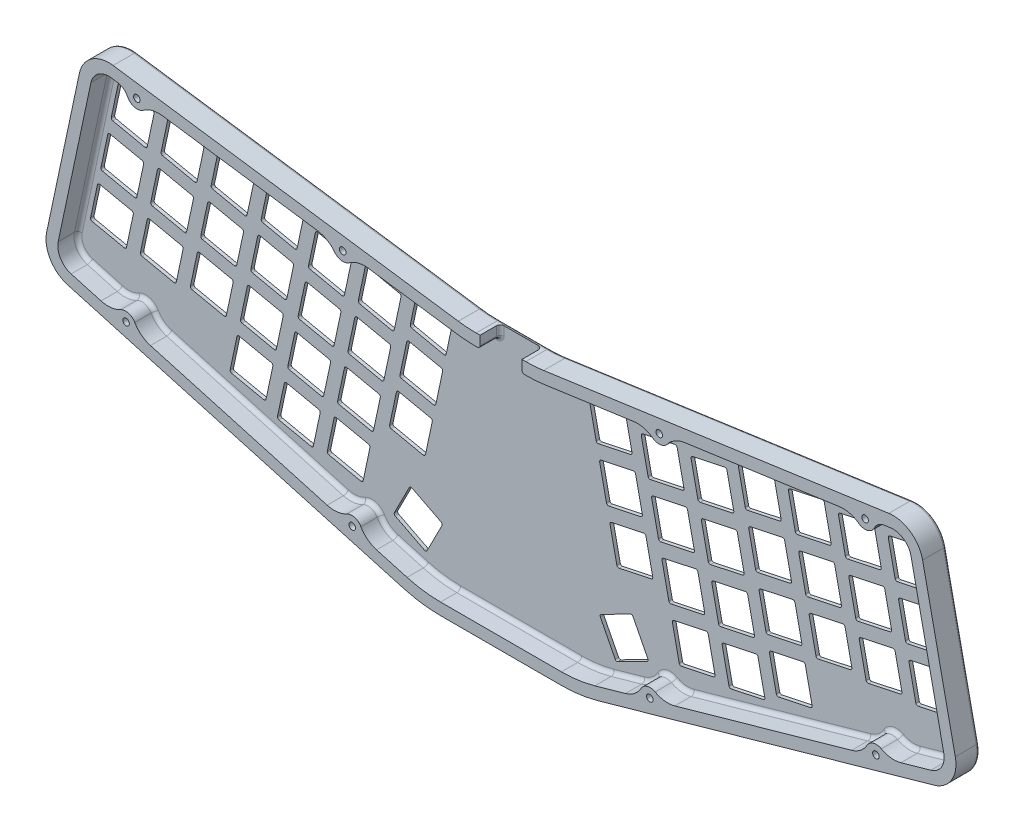
SolidWorks part; units mm, degrees
ref_plane "Front Plane" through (0, 0, 0) normal (0, 0, 1) x (1, 0, 0)
ref_plane "Top Plane" through (0, 0, 0) normal (0, 1, 0) x (1, 0, 0)
ref_plane "Right Plane" through (0, 0, 0) normal (1, 0, 0) x (0, 0, -1)
sketch "Model" plane through (0, 0, 0) normal (0, 0, 1) x (1, 0, 0)
  line L0 (7.1929, 63.9009) -> (19.4198, 61.302)
  line L1 (19.9974, 60.4125) -> (17.3986, 48.1856)
  line L2 (16.509, 47.6079) -> (4.2822, 50.2068)
  line L3 (3.7045, 51.0964) -> (6.3034, 63.3232)
  line L4 (3.2426, 45.3161) -> (15.4694, 42.7172)
  line L5 (16.0471, 41.8276) -> (13.4482, 29.6008)
  line L6 (12.5587, 29.0231) -> (0.3318, 31.622)
  line L7 (-0.2458, 32.5116) -> (2.3531, 44.7384)
  line L8 (-0.7077, 26.7313) -> (11.5191, 24.1324)
  line L9 (12.0968, 23.2428) -> (9.4979, 11.016)
  line L10 (8.6084, 10.4383) -> (-3.6185, 13.0372)
  line L11 (-4.1962, 13.9268) -> (-1.5973, 26.1536)
  line L12 (26.1936, 61.9069) -> (38.4204, 59.308)
  line L13 (38.9981, 58.4184) -> (36.3992, 46.1916)
  line L14 (35.5096, 45.6139) -> (23.2828, 48.2128)
  line L15 (22.7051, 49.1023) -> (25.304, 61.3292)
  line L16 (22.2432, 43.3221) -> (34.4701, 40.7232)
  line L17 (35.0478, 39.8336) -> (32.4489, 27.6068)
  line L18 (31.5593, 27.0291) -> (19.3325, 29.628)
  line L19 (18.7548, 30.5175) -> (21.3537, 42.7444)
  line L20 (18.2929, 24.7373) -> (30.5198, 22.1384)
  line L21 (31.0974, 21.2488) -> (28.4985, 9.022)
  line L22 (27.609, 8.4443) -> (15.3821, 11.0432)
  line L23 (14.8045, 11.9327) -> (17.4034, 24.1596)
  line L24 (45.2981, 60.4019) -> (57.525, 57.803)
  line L25 (58.1027, 56.9135) -> (55.5038, 44.6866)
  line L26 (54.6142, 44.109) -> (42.3874, 46.7078)
  line L27 (41.8097, 47.5974) -> (44.4086, 59.8242)
  line L28 (41.3478, 41.8171) -> (53.5747, 39.2182)
  line L29 (54.1523, 38.3287) -> (51.5534, 26.1018)
  line L30 (50.6639, 25.5241) -> (38.4371, 28.123)
  line L31 (37.8594, 29.0126) -> (40.4583, 41.2394)
  line L32 (37.3975, 23.2323) -> (49.6243, 20.6334)
  line L33 (50.202, 19.7439) -> (47.6031, 7.517)
  line L34 (46.7136, 6.9393) -> (34.4867, 9.5382)
  line L35 (33.9091, 10.4278) -> (36.5079, 22.6546)
  line L36 (64.4027, 58.897) -> (76.6296, 56.2981)
  line L37 (77.2072, 55.4085) -> (74.6083, 43.1817)
  line L38 (73.7188, 42.604) -> (61.492, 45.2029)
  line L39 (60.9143, 46.0924) -> (63.5132, 58.3193)
  line L40 (60.4524, 40.3122) -> (72.6792, 37.7133)
  line L41 (73.2569, 36.8237) -> (70.658, 24.5969)
  line L42 (69.7685, 24.0192) -> (57.5416, 26.6181)
  line L43 (56.964, 27.5076) -> (59.5629, 39.7345)
  line L44 (56.5021, 21.7274) -> (68.7289, 19.1285)
  line L45 (69.3066, 18.2389) -> (66.7077, 6.0121)
  line L46 (65.8182, 5.4344) -> (53.5913, 8.0333)
  line L47 (53.0136, 8.9228) -> (55.6125, 21.1497)
  line L48 (52.5518, 3.1425) -> (64.7786, 0.5437)
  line L49 (65.3563, -0.3459) -> (62.7574, -12.5727)
  line L50 (61.8678, -13.1504) -> (49.641, -10.5515)
  line L51 (49.0633, -9.662) -> (51.6622, 2.5649)
  line L52 (82.4677, 52.5013) -> (94.6946, 49.9024)
  line L53 (95.2723, 49.0128) -> (92.6734, 36.786)
  line L54 (91.7838, 36.2083) -> (79.557, 38.8072)
  line L55 (78.9793, 39.6967) -> (81.5782, 51.9236)
  line L56 (78.5174, 33.9165) -> (90.7443, 31.3176)
  line L57 (91.3219, 30.428) -> (88.723, 18.2012)
  line L58 (87.8335, 17.6235) -> (75.6067, 20.2224)
  line L59 (75.029, 21.1119) -> (77.6279, 33.3388)
  line L60 (74.5671, 15.3317) -> (86.7939, 12.7328)
  line L61 (87.3716, 11.8432) -> (84.7727, -0.3836)
  line L62 (83.8832, -0.9613) -> (71.6563, 1.6376)
  line L63 (71.0787, 2.5271) -> (73.6776, 14.754)
  line L64 (101.4684, 50.5072) -> (113.6952, 47.9083)
  line L65 (114.2729, 47.0188) -> (111.674, 34.792)
  line L66 (110.7845, 34.2143) -> (98.5576, 36.8132)
  line L67 (97.9799, 37.7027) -> (100.5788, 49.9296)
  line L68 (97.5181, 31.9224) -> (109.7449, 29.3235)
  line L69 (110.3226, 28.434) -> (107.7237, 16.2072)
  line L70 (106.8341, 15.6295) -> (94.6073, 18.2284)
  line L71 (94.0296, 19.1179) -> (96.6285, 31.3448)
  line L72 (93.5677, 13.3376) -> (105.7946, 10.7387)
  line L73 (106.3723, 9.8492) -> (103.7734, -2.3777)
  line L74 (102.8838, -2.9553) -> (90.657, -0.3564)
  line L75 (90.0793, 0.5331) -> (92.6782, 12.76)
  line L76 (134.1052, 48.9374) -> (131.5063, 36.7105)
  line L77 (130.6167, 36.1328) -> (118.3899, 38.7317)
  line L78 (117.8122, 39.6213) -> (120.4111, 51.8481)
  line L79 (117.3503, 33.841) -> (129.5772, 31.2421)
  line L80 (130.1548, 30.3526) -> (127.556, 18.1257)
  line L81 (126.6664, 17.548) -> (114.4396, 20.1469)
  line L82 (113.8619, 21.0365) -> (116.4608, 33.2633)
  line L83 (113.4, 15.2562) -> (125.6268, 12.6573)
  line L84 (126.2045, 11.7678) -> (123.6056, -0.4591)
  line L85 (122.7161, -1.0368) -> (110.4892, 1.5621)
  line L86 (109.9116, 2.4517) -> (112.5105, 14.6785)
  line L87 (70.6168, -3.2531) -> (82.8436, -5.852)
  line L88 (83.4213, -6.7416) -> (80.8224, -18.9684)
  line L89 (79.9329, -19.5461) -> (67.706, -16.9472)
  line L90 (67.1283, -16.0577) -> (69.7272, -3.8308)
  line L91 (89.6174, -5.2472) -> (101.8443, -7.8461)
  line L92 (102.4219, -8.7356) -> (99.823, -20.9625)
  line L93 (98.9335, -21.5401) -> (86.7066, -18.9412)
  line L94 (86.129, -18.0517) -> (88.7279, -5.8248)
  line L95 (117.654, -29.3648) -> (112.0852, -26.5274)
  line L96 (111.7574, -25.5186) -> (117.4323, -14.381)
  line L97 (118.4411, -14.0533) -> (129.5787, -19.7282)
  line L98 (129.9064, -20.7369) -> (124.2315, -31.8745)
  line L99 (123.2228, -32.2023) -> (117.654, -29.3648)
  line L100 (112.629, -33.5493) -> (124.2783, -36.8388)
  line L101 (137.0504, -38.6074) -> (160.1264, -38.6074)
  line L102 (160.1264, -38.6074) -> (183.2025, -38.6074)
  line L103 (195.9746, -36.8388) -> (207.6239, -33.5493)
  line L104 (226.4824, -28.2242) -> (271.949, -15.3856)
  line L105 (271.949, -15.3856) -> (293.9202, -9.1816)
  line L106 (210.7632, 57.9332) -> (177.0346, 53.1572)
  line L107 (169.604, 52.6338) -> (150.6488, 52.6338)
  line L108 (143.2182, 53.1572) -> (109.4896, 57.9332)
  line L109 (90.0873, 60.6806) -> (30.9176, 69.0589)
  line L110 (289.3352, 69.0589) -> (230.1656, 60.6806)
  line L111 (26.3327, -9.1816) -> (48.3039, -15.3856)
  line L112 (48.3039, -15.3856) -> (93.7705, -28.2242)
  line L113 (312.7787, -3.8564) -> (324.1811, -0.6367)
  line L114 (-2.1254, 39.3007) -> (3.622, 66.34)
  line L115 (-2.1254, 39.3007) -> (-8.8731, 7.5553)
  line L116 (13.8071, 71.4818) -> (11.4504, 71.8155)
  line L117 (-3.9283, -0.6367) -> (7.4742, -3.8564)
  line L118 (306.4458, 71.4818) -> (308.8024, 71.8155)
  line L119 (322.3782, 39.3007) -> (329.1259, 7.5553)
  line L120 (322.3782, 39.3007) -> (316.6308, 66.34)
  line L121 (121.3006, 52.4258) -> (133.5275, 49.8269)
  line L122 (313.0599, 63.9009) -> (300.8331, 61.302)
  line L123 (300.2554, 60.4125) -> (302.8543, 48.1856)
  line L124 (303.7438, 47.6079) -> (315.9707, 50.2068)
  line L125 (316.5483, 51.0964) -> (313.9494, 63.3232)
  line L126 (317.0102, 45.3161) -> (304.7834, 42.7172)
  line L127 (304.2057, 41.8276) -> (306.8046, 29.6008)
  line L128 (307.6941, 29.0231) -> (319.921, 31.622)
  line L129 (320.4987, 32.5116) -> (317.8998, 44.7384)
  line L130 (320.9605, 26.7313) -> (308.7337, 24.1324)
  line L131 (308.156, 23.2428) -> (310.7549, 11.016)
  line L132 (311.6445, 10.4383) -> (323.8713, 13.0372)
  line L133 (324.449, 13.9268) -> (321.8501, 26.1536)
  line L134 (294.0593, 61.9069) -> (281.8324, 59.308)
  line L135 (281.2548, 58.4184) -> (283.8536, 46.1916)
  line L136 (284.7432, 45.6139) -> (296.97, 48.2128)
  line L137 (297.5477, 49.1023) -> (294.9488, 61.3292)
  line L138 (298.0096, 43.3221) -> (285.7828, 40.7232)
  line L139 (285.2051, 39.8336) -> (287.804, 27.6068)
  line L140 (288.6935, 27.0291) -> (300.9204, 29.628)
  line L141 (301.498, 30.5175) -> (298.8991, 42.7444)
  line L142 (301.9599, 24.7373) -> (289.7331, 22.1384)
  line L143 (289.1554, 21.2488) -> (291.7543, 9.022)
  line L144 (292.6438, 8.4443) -> (304.8707, 11.0432)
  line L145 (305.4484, 11.9327) -> (302.8495, 24.1596)
  line L146 (274.9547, 60.4019) -> (262.7278, 57.803)
  line L147 (262.1502, 56.9135) -> (264.7491, 44.6866)
  line L148 (265.6386, 44.109) -> (277.8655, 46.7078)
  line L149 (278.4431, 47.5974) -> (275.8442, 59.8242)
  line L150 (278.905, 41.8171) -> (266.6782, 39.2182)
  line L151 (266.1005, 38.3287) -> (268.6994, 26.1018)
  line L152 (269.5889, 25.5241) -> (281.8158, 28.123)
  line L153 (282.3935, 29.0126) -> (279.7946, 41.2394)
  line L154 (282.8553, 23.2323) -> (270.6285, 20.6334)
  line L155 (270.0508, 19.7439) -> (272.6497, 7.517)
  line L156 (273.5393, 6.9393) -> (285.7661, 9.5382)
  line L157 (286.3438, 10.4278) -> (283.7449, 22.6546)
  line L158 (255.8501, 58.897) -> (243.6233, 56.2981)
  line L159 (243.0456, 55.4085) -> (245.6445, 43.1817)
  line L160 (246.534, 42.604) -> (258.7609, 45.2029)
  line L161 (259.3385, 46.0924) -> (256.7397, 58.3193)
  line L162 (259.8004, 40.3122) -> (247.5736, 37.7133)
  line L163 (246.9959, 36.8237) -> (249.5948, 24.5969)
  line L164 (250.4843, 24.0192) -> (262.7112, 26.6181)
  line L165 (263.2889, 27.5076) -> (260.69, 39.7345)
  line L166 (263.7508, 21.7274) -> (251.5239, 19.1285)
  line L167 (250.9462, 18.2389) -> (253.5451, 6.0121)
  line L168 (254.4347, 5.4344) -> (266.6615, 8.0333)
  line L169 (267.2392, 8.9228) -> (264.6403, 21.1497)
  line L170 (267.7011, 3.1425) -> (255.4742, 0.5437)
  line L171 (254.8966, -0.3459) -> (257.4954, -12.5727)
  line L172 (258.385, -13.1504) -> (270.6118, -10.5515)
  line L173 (271.1895, -9.662) -> (268.5906, 2.5649)
  line L174 (237.7851, 52.5013) -> (225.5582, 49.9024)
  line L175 (224.9806, 49.0128) -> (227.5795, 36.786)
  line L176 (228.469, 36.2083) -> (240.6958, 38.8072)
  line L177 (241.2735, 39.6967) -> (238.6746, 51.9236)
  line L178 (241.7354, 33.9165) -> (229.5086, 31.3176)
  line L179 (228.9309, 30.428) -> (231.5298, 18.2012)
  line L180 (232.4193, 17.6235) -> (244.6462, 20.2224)
  line L181 (245.2238, 21.1119) -> (242.6249, 33.3388)
  line L182 (245.6857, 15.3317) -> (233.4589, 12.7328)
  line L183 (232.8812, 11.8432) -> (235.4801, -0.3836)
  line L184 (236.3696, -0.9613) -> (248.5965, 1.6376)
  line L185 (249.1742, 2.5271) -> (246.5753, 14.754)
  line L186 (218.7845, 50.5072) -> (206.5576, 47.9083)
  line L187 (205.9799, 47.0188) -> (208.5788, 34.792)
  line L188 (209.4684, 34.2143) -> (221.6952, 36.8132)
  line L189 (222.2729, 37.7027) -> (219.674, 49.9296)
  line L190 (222.7348, 31.9224) -> (210.5079, 29.3235)
  line L191 (209.9303, 28.434) -> (212.5292, 16.2072)
  line L192 (213.4187, 15.6295) -> (225.6455, 18.2284)
  line L193 (226.2232, 19.1179) -> (223.6243, 31.3448)
  line L194 (226.6851, 13.3376) -> (214.4583, 10.7387)
  line L195 (213.8806, 9.8492) -> (216.4795, -2.3777)
  line L196 (217.369, -2.9553) -> (229.5959, -0.3564)
  line L197 (230.1735, 0.5331) -> (227.5746, 12.76)
  line L198 (186.1477, 48.9374) -> (188.7466, 36.7105)
  line L199 (189.6361, 36.1328) -> (201.8629, 38.7317)
  line L200 (202.4406, 39.6213) -> (199.8417, 51.8481)
  line L201 (202.9025, 33.841) -> (190.6757, 31.2421)
  line L202 (190.098, 30.3526) -> (192.6969, 18.1257)
  line L203 (193.5864, 17.548) -> (205.8133, 20.1469)
  line L204 (206.3909, 21.0365) -> (203.792, 33.2633)
  line L205 (206.8528, 15.2562) -> (194.626, 12.6573)
  line L206 (194.0483, 11.7678) -> (196.6472, -0.4591)
  line L207 (197.5367, -1.0368) -> (209.7636, 1.5621)
  line L208 (210.3413, 2.4517) -> (207.7424, 14.6785)
  line L209 (249.636, -3.2531) -> (237.4092, -5.852)
  line L210 (236.8315, -6.7416) -> (239.4304, -18.9684)
  line L211 (240.32, -19.5461) -> (252.5468, -16.9472)
  line L212 (253.1245, -16.0577) -> (250.5256, -3.8308)
  line L213 (230.6354, -5.2472) -> (218.4086, -7.8461)
  line L214 (217.8309, -8.7356) -> (220.4298, -20.9625)
  line L215 (221.3193, -21.5401) -> (233.5462, -18.9412)
  line L216 (234.1239, -18.0517) -> (231.525, -5.8248)
  line L217 (202.5988, -29.3648) -> (208.1676, -26.5274)
  line L218 (208.4954, -25.5186) -> (202.8205, -14.381)
  line L219 (201.8118, -14.0533) -> (190.6742, -19.7282)
  line L220 (190.3464, -20.7369) -> (196.0213, -31.8745)
  line L221 (197.03, -32.2023) -> (202.5988, -29.3648)
  line L222 (198.9522, 52.4258) -> (186.7253, 49.8269)
  line L223 (169.604, 55.6338) -> (150.6488, 55.6338)
  line L224 (143.6388, 56.1276) -> (11.8711, 74.7858)
  line L225 (0.6876, 66.9637) -> (-5.0598, 39.9244)
  line L226 (-5.0598, 39.9244) -> (-11.8075, 8.179)
  line L227 (-4.7435, -3.5238) -> (47.4886, -18.2727)
  line L228 (47.4886, -18.2727) -> (123.463, -39.7259)
  line L229 (137.0504, -41.6074) -> (160.1264, -41.6074)
  line L230 (160.1264, -41.6074) -> (183.2025, -41.6074)
  line L231 (196.7898, -39.7259) -> (272.7642, -18.2727)
  line L232 (272.7642, -18.2727) -> (324.9963, -3.5238)
  line L233 (332.0603, 8.179) -> (325.3126, 39.9244)
  line L234 (325.3126, 39.9244) -> (319.5653, 66.9637)
  line L235 (308.3818, 74.7858) -> (176.614, 56.1276)
  line L236 (169.604, 57.1338) -> (150.6488, 57.1338)
  line L237 (143.8491, 57.6128) -> (12.0814, 76.271)
  line L238 (-0.7797, 67.2756) -> (-6.527, 40.2363)
  line L239 (-6.527, 40.2363) -> (-13.2747, 8.4909)
  line L240 (-5.1511, -4.9673) -> (47.081, -19.7163)
  line L241 (47.081, -19.7163) -> (123.0554, -41.1694)
  line L242 (137.0504, -43.1074) -> (160.1264, -43.1074)
  line L243 (160.1264, -43.1074) -> (183.2025, -43.1074)
  line L244 (197.1974, -41.1694) -> (273.1718, -19.7163)
  line L245 (273.1718, -19.7163) -> (325.404, -4.9673)
  line L246 (333.5276, 8.4909) -> (326.7799, 40.2363)
  line L247 (326.7799, 40.2363) -> (321.0325, 67.2756)
  line L248 (308.1715, 76.271) -> (176.4037, 57.6128)
  arc A0 (106.6702, -28.8979) -> (101.2821, -27.3764) centre (103.1997, -30.8868) ccw
  arc A1 (93.7705, -28.2242) -> (101.2821, -27.3764) centre (96.4879, -18.6005) ccw
  arc A2 (106.6702, -28.8979) -> (112.629, -33.5493) centre (115.3464, -23.9256) ccw
  circle A3 centre (103.3356, -30.4056) radius 1.25
  arc A4 (207.6239, -33.5493) -> (213.5826, -28.8979) centre (204.9064, -23.9256) ccw
  arc A5 (218.9708, -27.3764) -> (226.4824, -28.2242) centre (223.7649, -18.6005) ccw
  arc A6 (218.9708, -27.3764) -> (213.5826, -28.8979) centre (217.0531, -30.8868) ccw
  circle A7 centre (216.9173, -30.4056) radius 1.25
  arc A8 (218.0932, 56.0855) -> (223.6367, 56.8704) centre (220.4644, 59.3069) ccw
  arc A9 (96.6161, 56.8704) -> (102.1596, 56.0855) centre (99.7884, 59.3069) ccw
  arc A10 (109.4896, 57.9332) -> (102.1596, 56.0855) centre (108.0876, 48.032) ccw
  arc A11 (96.6161, 56.8704) -> (90.0873, 60.6806) centre (88.6852, 50.7793) ccw
  arc A12 (218.0932, 56.0855) -> (210.7632, 57.9332) centre (212.1652, 48.032) ccw
  arc A13 (230.1656, 60.6806) -> (223.6367, 56.8704) centre (231.5676, 50.7793) ccw
  circle A14 centre (99.7183, 58.8118) radius 1.25
  circle A15 centre (220.5345, 58.8118) radius 1.25
  arc A16 (305.2671, -3.0086) -> (299.8789, -4.5301) centre (303.3494, -6.519) ccw
  arc A17 (20.3739, -4.5301) -> (14.9858, -3.0086) centre (16.9034, -6.519) ccw
  arc A18 (20.3739, -4.5301) -> (26.3327, -9.1816) centre (29.0501, 0.4421) ccw
  arc A19 (305.2671, -3.0086) -> (312.7787, -3.8564) centre (310.0612, 5.7673) ccw
  arc A20 (293.9202, -9.1816) -> (299.8789, -4.5301) centre (291.2027, 0.4421) ccw
  arc A21 (7.4742, -3.8564) -> (14.9858, -3.0086) centre (10.1916, 5.7673) ccw
  circle A22 centre (17.0393, -6.0378) radius 1.25
  circle A23 centre (303.2135, -6.0378) radius 1.25
  arc A24 (-8.8731, 7.5553) -> (-3.9283, -0.6367) centre (-2.026, 6.0999) ccw
  arc A25 (11.4504, 71.8155) -> (3.622, 66.34) centre (10.469, 64.8846) ccw
  arc A26 (316.6308, 66.34) -> (308.8024, 71.8155) centre (309.7838, 64.8846) ccw
  arc A27 (324.1811, -0.6367) -> (329.1259, 7.5553) centre (322.2789, 6.0999) ccw
  arc A28 (296.6652, 67.2112) -> (302.641, 68.6986) centre (299.0364, 70.4326) ccw
  arc A29 (17.6118, 68.6986) -> (23.5876, 67.2112) centre (21.2165, 70.4326) ccw
  arc A30 (30.9176, 69.0589) -> (23.5876, 67.2112) centre (29.5156, 59.1577) ccw
  arc A31 (17.6118, 68.6986) -> (13.8071, 71.4818) centre (13.106, 66.5312) ccw
  arc A32 (306.4458, 71.4818) -> (302.641, 68.6986) centre (307.1468, 66.5312) ccw
  arc A33 (296.6652, 67.2112) -> (289.3352, 69.0589) centre (290.7372, 59.1577) ccw
  circle A34 centre (299.1065, 69.9376) radius 1.25
  circle A35 centre (21.1464, 69.9376) radius 1.25
  arc A36 (3.7045, 51.0964) -> (4.2822, 50.2068) centre (4.4381, 50.9404) ccw
  arc A37 (7.1929, 63.9009) -> (6.3034, 63.3232) centre (7.037, 63.1673) ccw
  arc A38 (19.9974, 60.4125) -> (19.4198, 61.302) centre (19.2638, 60.5684) ccw
  arc A39 (16.509, 47.6079) -> (17.3986, 48.1856) centre (16.6649, 48.3415) ccw
  arc A40 (3.2426, 45.3161) -> (2.3531, 44.7384) centre (3.0867, 44.5825) ccw
  arc A41 (-0.2458, 32.5116) -> (0.3318, 31.622) centre (0.4878, 32.3556) ccw
  arc A42 (12.5587, 29.0231) -> (13.4482, 29.6008) centre (12.7146, 29.7567) ccw
  arc A43 (16.0471, 41.8276) -> (15.4694, 42.7172) centre (15.3135, 41.9836) ccw
  arc A44 (-0.7077, 26.7313) -> (-1.5973, 26.1536) centre (-0.8637, 25.9977) ccw
  arc A45 (-4.1962, 13.9268) -> (-3.6185, 13.0372) centre (-3.4625, 13.7708) ccw
  arc A46 (8.6084, 10.4383) -> (9.4979, 11.016) centre (8.7643, 11.1719) ccw
  arc A47 (12.0968, 23.2428) -> (11.5191, 24.1324) centre (11.3632, 23.3988) ccw
  arc A48 (14.8045, 11.9327) -> (15.3821, 11.0432) centre (15.5381, 11.7768) ccw
  arc A49 (27.609, 8.4443) -> (28.4985, 9.022) centre (27.7649, 9.1779) ccw
  arc A50 (31.0974, 21.2488) -> (30.5198, 22.1384) centre (30.3638, 21.4048) ccw
  arc A51 (18.2929, 24.7373) -> (17.4034, 24.1596) centre (18.137, 24.0036) ccw
  arc A52 (18.7548, 30.5175) -> (19.3325, 29.628) centre (19.4884, 30.3616) ccw
  arc A53 (31.5593, 27.0291) -> (32.4489, 27.6068) centre (31.7152, 27.7627) ccw
  arc A54 (35.0478, 39.8336) -> (34.4701, 40.7232) centre (34.3141, 39.9896) ccw
  arc A55 (22.2432, 43.3221) -> (21.3537, 42.7444) centre (22.0873, 42.5885) ccw
  arc A56 (22.7051, 49.1023) -> (23.2828, 48.2128) centre (23.4387, 48.9464) ccw
  arc A57 (35.5096, 45.6139) -> (36.3992, 46.1916) centre (35.6656, 46.3475) ccw
  arc A58 (38.9981, 58.4184) -> (38.4204, 59.308) centre (38.2645, 58.5744) ccw
  arc A59 (26.1936, 61.9069) -> (25.304, 61.3292) centre (26.0376, 61.1733) ccw
  arc A60 (33.9091, 10.4278) -> (34.4867, 9.5382) centre (34.6427, 10.2718) ccw
  arc A61 (37.3975, 23.2323) -> (36.5079, 22.6546) centre (37.2416, 22.4987) ccw
  arc A62 (50.202, 19.7439) -> (49.6243, 20.6334) centre (49.4684, 19.8998) ccw
  arc A63 (46.7136, 6.9393) -> (47.6031, 7.517) centre (46.8695, 7.673) ccw
  arc A64 (50.6639, 25.5241) -> (51.5534, 26.1018) centre (50.8198, 26.2578) ccw
  arc A65 (37.8594, 29.0126) -> (38.4371, 28.123) centre (38.593, 28.8567) ccw
  arc A66 (41.3478, 41.8171) -> (40.4583, 41.2394) centre (41.1919, 41.0835) ccw
  arc A67 (54.1523, 38.3287) -> (53.5747, 39.2182) centre (53.4187, 38.4846) ccw
  arc A68 (54.6142, 44.109) -> (55.5038, 44.6866) centre (54.7702, 44.8426) ccw
  arc A69 (41.8097, 47.5974) -> (42.3874, 46.7078) centre (42.5433, 47.4415) ccw
  arc A70 (45.2981, 60.4019) -> (44.4086, 59.8242) centre (45.1422, 59.6683) ccw
  arc A71 (58.1027, 56.9135) -> (57.525, 57.803) centre (57.369, 57.0694) ccw
  arc A72 (56.964, 27.5076) -> (57.5416, 26.6181) centre (57.6976, 27.3517) ccw
  arc A73 (60.4524, 40.3122) -> (59.5629, 39.7345) centre (60.2965, 39.5785) ccw
  arc A74 (73.2569, 36.8237) -> (72.6792, 37.7133) centre (72.5233, 36.9797) ccw
  arc A75 (69.7685, 24.0192) -> (70.658, 24.5969) centre (69.9244, 24.7528) ccw
  arc A76 (60.9143, 46.0924) -> (61.492, 45.2029) centre (61.6479, 45.9365) ccw
  arc A77 (73.7188, 42.604) -> (74.6083, 43.1817) centre (73.8747, 43.3376) ccw
  arc A78 (77.2072, 55.4085) -> (76.6296, 56.2981) centre (76.4736, 55.5645) ccw
  arc A79 (64.4027, 58.897) -> (63.5132, 58.3193) centre (64.2468, 58.1634) ccw
  arc A80 (53.0136, 8.9228) -> (53.5913, 8.0333) centre (53.7472, 8.7669) ccw
  arc A81 (56.5021, 21.7274) -> (55.6125, 21.1497) centre (56.3461, 20.9937) ccw
  arc A82 (69.3066, 18.2389) -> (68.7289, 19.1285) centre (68.573, 18.3948) ccw
  arc A83 (65.8182, 5.4344) -> (66.7077, 6.0121) centre (65.9741, 6.168) ccw
  arc A84 (49.0633, -9.662) -> (49.641, -10.5515) centre (49.7969, -9.8179) ccw
  arc A85 (52.5518, 3.1425) -> (51.6622, 2.5649) centre (52.3958, 2.4089) ccw
  arc A86 (65.3563, -0.3459) -> (64.7786, 0.5437) centre (64.6227, -0.19) ccw
  arc A87 (61.8678, -13.1504) -> (62.7574, -12.5727) centre (62.0238, -12.4168) ccw
  arc A88 (67.1283, -16.0577) -> (67.706, -16.9472) centre (67.8619, -16.2136) ccw
  arc A89 (70.6168, -3.2531) -> (69.7272, -3.8308) centre (70.4608, -3.9868) ccw
  arc A90 (83.4213, -6.7416) -> (82.8436, -5.852) centre (82.6877, -6.5856) ccw
  arc A91 (79.9329, -19.5461) -> (80.8224, -18.9684) centre (80.0888, -18.8125) ccw
  arc A92 (71.0787, 2.5271) -> (71.6563, 1.6376) centre (71.8123, 2.3712) ccw
  arc A93 (83.8832, -0.9613) -> (84.7727, -0.3836) centre (84.0391, -0.2277) ccw
  arc A94 (87.3716, 11.8432) -> (86.7939, 12.7328) centre (86.638, 11.9992) ccw
  arc A95 (74.5671, 15.3317) -> (73.6776, 14.754) centre (74.4112, 14.5981) ccw
  arc A96 (75.029, 21.1119) -> (75.6067, 20.2224) centre (75.7626, 20.956) ccw
  arc A97 (87.8335, 17.6235) -> (88.723, 18.2012) centre (87.9894, 18.3571) ccw
  arc A98 (91.3219, 30.428) -> (90.7443, 31.3176) centre (90.5883, 30.584) ccw
  arc A99 (78.5174, 33.9165) -> (77.6279, 33.3388) centre (78.3615, 33.1829) ccw
  arc A100 (78.9793, 39.6967) -> (79.557, 38.8072) centre (79.7129, 39.5408) ccw
  arc A101 (82.4677, 52.5013) -> (81.5782, 51.9236) centre (82.3118, 51.7677) ccw
  arc A102 (95.2723, 49.0128) -> (94.6946, 49.9024) centre (94.5387, 49.1688) ccw
  arc A103 (91.7838, 36.2083) -> (92.6734, 36.786) centre (91.9398, 36.9419) ccw
  arc A104 (97.9799, 37.7027) -> (98.5576, 36.8132) centre (98.7135, 37.5468) ccw
  arc A105 (101.4684, 50.5072) -> (100.5788, 49.9296) centre (101.3124, 49.7736) ccw
  arc A106 (114.2729, 47.0188) -> (113.6952, 47.9083) centre (113.5393, 47.1747) ccw
  arc A107 (110.7845, 34.2143) -> (111.674, 34.792) centre (110.9404, 34.9479) ccw
  arc A108 (97.5181, 31.9224) -> (96.6285, 31.3448) centre (97.3621, 31.1888) ccw
  arc A109 (110.3226, 28.434) -> (109.7449, 29.3235) centre (109.589, 28.5899) ccw
  arc A110 (106.8341, 15.6295) -> (107.7237, 16.2072) centre (106.9901, 16.3631) ccw
  arc A111 (94.0296, 19.1179) -> (94.6073, 18.2284) centre (94.7632, 18.962) ccw
  arc A112 (93.5677, 13.3376) -> (92.6782, 12.76) centre (93.4118, 12.604) ccw
  arc A113 (106.3723, 9.8492) -> (105.7946, 10.7387) centre (105.6386, 10.0051) ccw
  arc A114 (102.8838, -2.9553) -> (103.7734, -2.3777) centre (103.0397, -2.2217) ccw
  arc A115 (90.0793, 0.5331) -> (90.657, -0.3564) centre (90.8129, 0.3772) ccw
  arc A116 (89.6174, -5.2472) -> (88.7279, -5.8248) centre (89.4615, -5.9808) ccw
  arc A117 (102.4219, -8.7356) -> (101.8443, -7.8461) centre (101.6883, -8.5797) ccw
  arc A118 (98.9335, -21.5401) -> (99.823, -20.9625) centre (99.0894, -20.8065) ccw
  arc A119 (86.129, -18.0517) -> (86.7066, -18.9412) centre (86.8626, -18.2076) ccw
  arc A120 (111.7574, -25.5186) -> (112.0852, -26.5274) centre (112.4257, -25.8591) ccw
  arc A121 (118.4411, -14.0533) -> (117.4323, -14.381) centre (118.1006, -14.7215) ccw
  arc A122 (129.9064, -20.7369) -> (129.5787, -19.7282) centre (129.2382, -20.3964) ccw
  arc A123 (123.2228, -32.2023) -> (124.2315, -31.8745) centre (123.5633, -31.534) ccw
  arc A124 (109.9116, 2.4517) -> (110.4892, 1.5621) centre (110.6452, 2.2957) ccw
  arc A125 (122.7161, -1.0368) -> (123.6056, -0.4591) centre (122.872, -0.3032) ccw
  arc A126 (126.2045, 11.7678) -> (125.6268, 12.6573) centre (125.4709, 11.9237) ccw
  arc A127 (113.4, 15.2562) -> (112.5105, 14.6785) centre (113.2441, 14.5226) ccw
  arc A128 (113.8619, 21.0365) -> (114.4396, 20.1469) centre (114.5955, 20.8805) ccw
  arc A129 (126.6664, 17.548) -> (127.556, 18.1257) centre (126.8223, 18.2817) ccw
  arc A130 (130.1548, 30.3526) -> (129.5772, 31.2421) centre (129.4212, 30.5085) ccw
  arc A131 (117.3503, 33.841) -> (116.4608, 33.2633) centre (117.1944, 33.1074) ccw
  arc A132 (117.8122, 39.6213) -> (118.3899, 38.7317) centre (118.5458, 39.4654) ccw
  arc A133 (130.6167, 36.1328) -> (131.5063, 36.7105) centre (130.7727, 36.8665) ccw
  arc A134 (134.1052, 48.9374) -> (133.5275, 49.8269) centre (133.3716, 49.0933) ccw
  arc A135 (121.3006, 52.4258) -> (120.4111, 51.8481) centre (121.1447, 51.6922) ccw
  arc A136 (313.9494, 63.3232) -> (313.0599, 63.9009) centre (313.2158, 63.1673) ccw
  arc A137 (300.8331, 61.302) -> (300.2554, 60.4125) centre (300.989, 60.5684) ccw
  arc A138 (302.8543, 48.1856) -> (303.7438, 47.6079) centre (303.5879, 48.3415) ccw
  arc A139 (315.9707, 50.2068) -> (316.5483, 51.0964) centre (315.8147, 50.9404) ccw
  arc A140 (317.8998, 44.7384) -> (317.0102, 45.3161) centre (317.1662, 44.5825) ccw
  arc A141 (304.7834, 42.7172) -> (304.2057, 41.8276) centre (304.9393, 41.9836) ccw
  arc A142 (306.8046, 29.6008) -> (307.6941, 29.0231) centre (307.5382, 29.7567) ccw
  arc A143 (319.921, 31.622) -> (320.4987, 32.5116) centre (319.7651, 32.3556) ccw
  arc A144 (321.8501, 26.1536) -> (320.9605, 26.7313) centre (321.1165, 25.9977) ccw
  arc A145 (308.7337, 24.1324) -> (308.156, 23.2428) centre (308.8896, 23.3988) ccw
  arc A146 (310.7549, 11.016) -> (311.6445, 10.4383) centre (311.4885, 11.1719) ccw
  arc A147 (323.8713, 13.0372) -> (324.449, 13.9268) centre (323.7154, 13.7708) ccw
  arc A148 (294.9488, 61.3292) -> (294.0593, 61.9069) centre (294.2152, 61.1733) ccw
  arc A149 (281.8324, 59.308) -> (281.2548, 58.4184) centre (281.9884, 58.5744) ccw
  arc A150 (283.8536, 46.1916) -> (284.7432, 45.6139) centre (284.5873, 46.3475) ccw
  arc A151 (296.97, 48.2128) -> (297.5477, 49.1023) centre (296.8141, 48.9464) ccw
  arc A152 (298.8991, 42.7444) -> (298.0096, 43.3221) centre (298.1655, 42.5885) ccw
  arc A153 (285.7828, 40.7232) -> (285.2051, 39.8336) centre (285.9387, 39.9896) ccw
  arc A154 (287.804, 27.6068) -> (288.6935, 27.0291) centre (288.5376, 27.7627) ccw
  arc A155 (300.9204, 29.628) -> (301.498, 30.5175) centre (300.7644, 30.3616) ccw
  arc A156 (302.8495, 24.1596) -> (301.9599, 24.7373) centre (302.1159, 24.0036) ccw
  arc A157 (289.7331, 22.1384) -> (289.1554, 21.2488) centre (289.889, 21.4048) ccw
  arc A158 (291.7543, 9.022) -> (292.6438, 8.4443) centre (292.4879, 9.1779) ccw
  arc A159 (304.8707, 11.0432) -> (305.4484, 11.9327) centre (304.7147, 11.7768) ccw
  arc A160 (262.7278, 57.803) -> (262.1502, 56.9135) centre (262.8838, 57.0694) ccw
  arc A161 (275.8442, 59.8242) -> (274.9547, 60.4019) centre (275.1106, 59.6683) ccw
  arc A162 (264.7491, 44.6866) -> (265.6386, 44.109) centre (265.4827, 44.8426) ccw
  arc A163 (277.8655, 46.7078) -> (278.4431, 47.5974) centre (277.7095, 47.4415) ccw
  arc A164 (266.6782, 39.2182) -> (266.1005, 38.3287) centre (266.8341, 38.4846) ccw
  arc A165 (279.7946, 41.2394) -> (278.905, 41.8171) centre (279.0609, 41.0835) ccw
  arc A166 (268.6994, 26.1018) -> (269.5889, 25.5241) centre (269.433, 26.2578) ccw
  arc A167 (281.8158, 28.123) -> (282.3935, 29.0126) centre (281.6598, 28.8567) ccw
  arc A168 (270.6285, 20.6334) -> (270.0508, 19.7439) centre (270.7844, 19.8998) ccw
  arc A169 (283.7449, 22.6546) -> (282.8553, 23.2323) centre (283.0113, 22.4987) ccw
  arc A170 (272.6497, 7.517) -> (273.5393, 6.9393) centre (273.3833, 7.673) ccw
  arc A171 (285.7661, 9.5382) -> (286.3438, 10.4278) centre (285.6102, 10.2718) ccw
  arc A172 (256.7397, 58.3193) -> (255.8501, 58.897) centre (256.006, 58.1634) ccw
  arc A173 (243.6233, 56.2981) -> (243.0456, 55.4085) centre (243.7792, 55.5645) ccw
  arc A174 (245.6445, 43.1817) -> (246.534, 42.604) centre (246.3781, 43.3376) ccw
  arc A175 (258.7609, 45.2029) -> (259.3385, 46.0924) centre (258.6049, 45.9365) ccw
  arc A176 (247.5736, 37.7133) -> (246.9959, 36.8237) centre (247.7295, 36.9797) ccw
  arc A177 (260.69, 39.7345) -> (259.8004, 40.3122) centre (259.9564, 39.5785) ccw
  arc A178 (249.5948, 24.5969) -> (250.4843, 24.0192) centre (250.3284, 24.7528) ccw
  arc A179 (262.7112, 26.6181) -> (263.2889, 27.5076) centre (262.5553, 27.3517) ccw
  arc A180 (251.5239, 19.1285) -> (250.9462, 18.2389) centre (251.6798, 18.3948) ccw
  arc A181 (253.5451, 6.0121) -> (254.4347, 5.4344) centre (254.2787, 6.168) ccw
  arc A182 (264.6403, 21.1497) -> (263.7508, 21.7274) centre (263.9067, 20.9937) ccw
  arc A183 (266.6615, 8.0333) -> (267.2392, 8.9228) centre (266.5056, 8.7669) ccw
  arc A184 (255.4742, 0.5437) -> (254.8966, -0.3459) centre (255.6302, -0.19) ccw
  arc A185 (257.4954, -12.5727) -> (258.385, -13.1504) centre (258.2291, -12.4168) ccw
  arc A186 (268.5906, 2.5649) -> (267.7011, 3.1425) centre (267.857, 2.4089) ccw
  arc A187 (270.6118, -10.5515) -> (271.1895, -9.662) centre (270.4559, -9.8179) ccw
  arc A188 (225.5582, 49.9024) -> (224.9806, 49.0128) centre (225.7142, 49.1688) ccw
  arc A189 (238.6746, 51.9236) -> (237.7851, 52.5013) centre (237.941, 51.7677) ccw
  arc A190 (227.5795, 36.786) -> (228.469, 36.2083) centre (228.3131, 36.9419) ccw
  arc A191 (240.6958, 38.8072) -> (241.2735, 39.6967) centre (240.5399, 39.5408) ccw
  arc A192 (242.6249, 33.3388) -> (241.7354, 33.9165) centre (241.8913, 33.1829) ccw
  arc A193 (229.5086, 31.3176) -> (228.9309, 30.428) centre (229.6645, 30.584) ccw
  arc A194 (231.5298, 18.2012) -> (232.4193, 17.6235) centre (232.2634, 18.3571) ccw
  arc A195 (244.6462, 20.2224) -> (245.2238, 21.1119) centre (244.4902, 20.956) ccw
  arc A196 (246.5753, 14.754) -> (245.6857, 15.3317) centre (245.8417, 14.5981) ccw
  arc A197 (233.4589, 12.7328) -> (232.8812, 11.8432) centre (233.6148, 11.9992) ccw
  arc A198 (235.4801, -0.3836) -> (236.3696, -0.9613) centre (236.2137, -0.2277) ccw
  arc A199 (248.5965, 1.6376) -> (249.1742, 2.5271) centre (248.4406, 2.3712) ccw
  arc A200 (206.5576, 47.9083) -> (205.9799, 47.0188) centre (206.7135, 47.1747) ccw
  arc A201 (219.674, 49.9296) -> (218.7845, 50.5072) centre (218.9404, 49.7736) ccw
  arc A202 (208.5788, 34.792) -> (209.4684, 34.2143) centre (209.3124, 34.9479) ccw
  arc A203 (221.6952, 36.8132) -> (222.2729, 37.7027) centre (221.5393, 37.5468) ccw
  arc A204 (210.5079, 29.3235) -> (209.9303, 28.434) centre (210.6639, 28.5899) ccw
  arc A205 (223.6243, 31.3448) -> (222.7348, 31.9224) centre (222.8907, 31.1888) ccw
  arc A206 (212.5292, 16.2072) -> (213.4187, 15.6295) centre (213.2628, 16.3631) ccw
  arc A207 (225.6455, 18.2284) -> (226.2232, 19.1179) centre (225.4896, 18.962) ccw
  arc A208 (227.5746, 12.76) -> (226.6851, 13.3376) centre (226.841, 12.604) ccw
  arc A209 (216.4795, -2.3777) -> (217.369, -2.9553) centre (217.2131, -2.2217) ccw
  arc A210 (214.4583, 10.7387) -> (213.8806, 9.8492) centre (214.6142, 10.0051) ccw
  arc A211 (229.5959, -0.3564) -> (230.1735, 0.5331) centre (229.4399, 0.3772) ccw
  arc A212 (199.8417, 51.8481) -> (198.9522, 52.4258) centre (199.1081, 51.6922) ccw
  arc A213 (186.7253, 49.8269) -> (186.1477, 48.9374) centre (186.8813, 49.0933) ccw
  arc A214 (188.7466, 36.7105) -> (189.6361, 36.1328) centre (189.4802, 36.8665) ccw
  arc A215 (201.8629, 38.7317) -> (202.4406, 39.6213) centre (201.707, 39.4654) ccw
  arc A216 (203.792, 33.2633) -> (202.9025, 33.841) centre (203.0584, 33.1074) ccw
  arc A217 (190.6757, 31.2421) -> (190.098, 30.3526) centre (190.8316, 30.5085) ccw
  arc A218 (192.6969, 18.1257) -> (193.5864, 17.548) centre (193.4305, 18.2817) ccw
  arc A219 (205.8133, 20.1469) -> (206.3909, 21.0365) centre (205.6573, 20.8805) ccw
  arc A220 (207.7424, 14.6785) -> (206.8528, 15.2562) centre (207.0088, 14.5226) ccw
  arc A221 (194.626, 12.6573) -> (194.0483, 11.7678) centre (194.7819, 11.9237) ccw
  arc A222 (196.6472, -0.4591) -> (197.5367, -1.0368) centre (197.3808, -0.3032) ccw
  arc A223 (209.7636, 1.5621) -> (210.3413, 2.4517) centre (209.6077, 2.2957) ccw
  arc A224 (250.5256, -3.8308) -> (249.636, -3.2531) centre (249.792, -3.9868) ccw
  arc A225 (239.4304, -18.9684) -> (240.32, -19.5461) centre (240.164, -18.8125) ccw
  arc A226 (237.4092, -5.852) -> (236.8315, -6.7416) centre (237.5651, -6.5856) ccw
  arc A227 (252.5468, -16.9472) -> (253.1245, -16.0577) centre (252.3909, -16.2136) ccw
  arc A228 (218.4086, -7.8461) -> (217.8309, -8.7356) centre (218.5645, -8.5797) ccw
  arc A229 (231.525, -5.8248) -> (230.6354, -5.2472) centre (230.7914, -5.9808) ccw
  arc A230 (220.4298, -20.9625) -> (221.3193, -21.5401) centre (221.1634, -20.8065) ccw
  arc A231 (233.5462, -18.9412) -> (234.1239, -18.0517) centre (233.3903, -18.2076) ccw
  arc A232 (208.1676, -26.5274) -> (208.4954, -25.5186) centre (207.8271, -25.8591) ccw
  arc A233 (190.6742, -19.7282) -> (190.3464, -20.7369) centre (191.0147, -20.3964) ccw
  arc A234 (202.8205, -14.381) -> (201.8118, -14.0533) centre (202.1522, -14.7215) ccw
  arc A235 (196.0213, -31.8745) -> (197.03, -32.2023) centre (196.6895, -31.534) ccw
  arc A236 (124.2783, -36.8388) -> (137.0504, -38.6074) centre (137.0504, 8.3926) ccw
  arc A237 (183.2025, -38.6074) -> (195.9746, -36.8388) centre (183.2025, 8.3926) ccw
  arc A238 (169.604, 52.6338) -> (177.0346, 53.1572) centre (169.604, 105.6338) ccw
  arc A239 (143.2182, 53.1572) -> (150.6488, 52.6338) centre (150.6488, 105.6338) ccw
  arc A240 (169.604, 55.6338) -> (176.614, 56.1276) centre (169.604, 105.6338) ccw
  arc A241 (143.6388, 56.1276) -> (150.6488, 55.6338) centre (150.6488, 105.6338) ccw
  arc A242 (11.8711, 74.7858) -> (0.6876, 66.9637) centre (10.469, 64.8846) ccw
  arc A243 (-11.8075, 8.179) -> (-4.7435, -3.5238) centre (-2.026, 6.0999) ccw
  arc A244 (123.463, -39.7259) -> (137.0504, -41.6074) centre (137.0504, 8.3926) ccw
  arc A245 (183.2025, -41.6074) -> (196.7898, -39.7259) centre (183.2025, 8.3926) ccw
  arc A246 (324.9963, -3.5238) -> (332.0603, 8.179) centre (322.2789, 6.0999) ccw
  arc A247 (319.5653, 66.9637) -> (308.3818, 74.7858) centre (309.7838, 64.8846) ccw
  arc A248 (169.604, 57.1338) -> (176.4037, 57.6128) centre (169.604, 105.6338) ccw
  arc A249 (143.8491, 57.6128) -> (150.6488, 57.1338) centre (150.6488, 105.6338) ccw
  arc A250 (12.0814, 76.271) -> (-0.7797, 67.2756) centre (10.469, 64.8846) ccw
  arc A251 (-13.2747, 8.4909) -> (-5.1511, -4.9673) centre (-2.026, 6.0999) ccw
  arc A252 (123.0554, -41.1694) -> (137.0504, -43.1074) centre (137.0504, 8.3926) ccw
  arc A253 (183.2025, -43.1074) -> (197.1974, -41.1694) centre (183.2025, 8.3926) ccw
  arc A254 (325.404, -4.9673) -> (333.5276, 8.4909) centre (322.2789, 6.0999) ccw
  arc A255 (321.0325, 67.2756) -> (308.1715, 76.271) centre (309.7838, 64.8846) ccw
extrude "Boss-Extrude1" add sketch "Model" along normal blind 9 contours L247 A255 L248 A248 L236 A249 L237 A250 L238 L239 A251 L240 L241 A252 L242 L243 A253 L244 L245 A254 L246 A247 L234 L233 A246 L232 L231 A245 L230 L229 A244 L228 L227 A243 L226 L225 A242 L224 A241 L223 A240 L235 | L234 A247 L235 A240 L223 A241 L224 A242 L225 L226 A243 L227 L228 A244 L229 L230 A245 L231 L232 A246 L233 L108 A239 L107 A238 L106 A12 A8 A13 L110 A33 A28 A32 L118 A26 L120 L119 A27 L113 A19 A16 A20 L105 L104 A5 A6 A4 L103 A237 L102 region at (173.1432, 55.3948, 0) region at (173.0381, 56.8873, 0)
extrude "Boss-Extrude2" add sketch "Model<3>" along normal blind 1.3 contours A239 L108 A10 A9 A11 L109 A30 A29 A31 L116 A25 L114 L115 A24 L117 A21 A17 A18 L111 L112 A1 A0 A2 L100 A236 L101 L102 A237 L103 A4 A6 A5 L104 L105 A20 A16 A19 L113 A27 L119 L120 A26 L118 A32 A28 A33 L110 A13 A8 A12 L106 region at (160.1264, 15.6084, 0)
sketch "Model<3>" plane through (0, 0, 0) normal (0, 0, 1) x (1, 0, 0) same geometry as "Model"
extrude "Boss-Extrude3" add sketch "Model<4>" along normal blind 2 contours A22 | A3 | A14 | A7 | A15 | A34 | A23 | A35 region at (103.3356, -30.4056, 0) region at (216.9173, -30.4056, 0) region at (99.7183, 58.8118, 0) region at (220.5345, 58.8118, 0) region at (17.0393, -6.0378, 0) region at (303.2135, -6.0378, 0) region at (299.1065, 69.9376, 0)
sketch "Model<4>" plane through (0, 0, 0) normal (0, 0, 1) x (1, 0, 0) same geometry as "Model"
sketch "Sketch3" plane through (0, 57.1338, 0) normal (0, 1, 0) x (1, 0, 0)
  line L1 (169.604, -9) -> (150.6488, -9) construction
  line L2 (160.1264, -1.3) -> (168.1264, -1.3)
  line L3 (168.1264, -1.3) -> (168.1264, -9)
  line L4 (168.1264, -9) -> (160.1264, -9)
  line L5 (160.1264, -9) -> (152.1264, -9)
  line L6 (152.1264, -9) -> (152.1264, -1.3)
  line L7 (152.1264, -1.3) -> (160.1264, -1.3)
extrude "Cut-Extrude1" cut sketch "Sketch3" against normal blind 10
fillet "Fillet2" radius 1 1 edges at (152.1264, 52.6338, 5.15) type face fillet first side face at (152.1264, 54.8838, 5.15) second side face at (151.3876, 52.6338, 5.15)
fillet "Fillet3" radius 1 1 edges at (168.1264, 52.6338, 5.15) type face fillet first side face at (168.1264, 54.8838, 5.15) second side face at (168.8652, 52.6338, 5.15)
fillet "Fillet4" radius 1.5 1 edges at (146.9243, 52.7648, 1.3) type face fillet first side face at (146.9289, 52.8302, 5.15) second side face at (160.1264, 26.2067, 1.3)
fillet "Fillet6" radius 1 16 edges at (147.2405, 57.2537, 0) (160.1264, 57.1338, 0) (173.0123, 57.2537, 0) (242.2876, 66.9419, 0) (316.375, 74.3083, 0) (327.28, 37.8832, 0) (332.1243, 0.157, 0) (261.3007, -23.0684, 0) (190.2667, -42.6206, 0) (160.1264, -43.1074, 0) (129.9861, -42.6206, 0) (58.9521, -23.0684, 0) (-11.8715, 0.157, 0) (-7.0272, 37.8832, 0) (3.8778, 74.3083, 0) (77.9652, 66.9419, 0)
